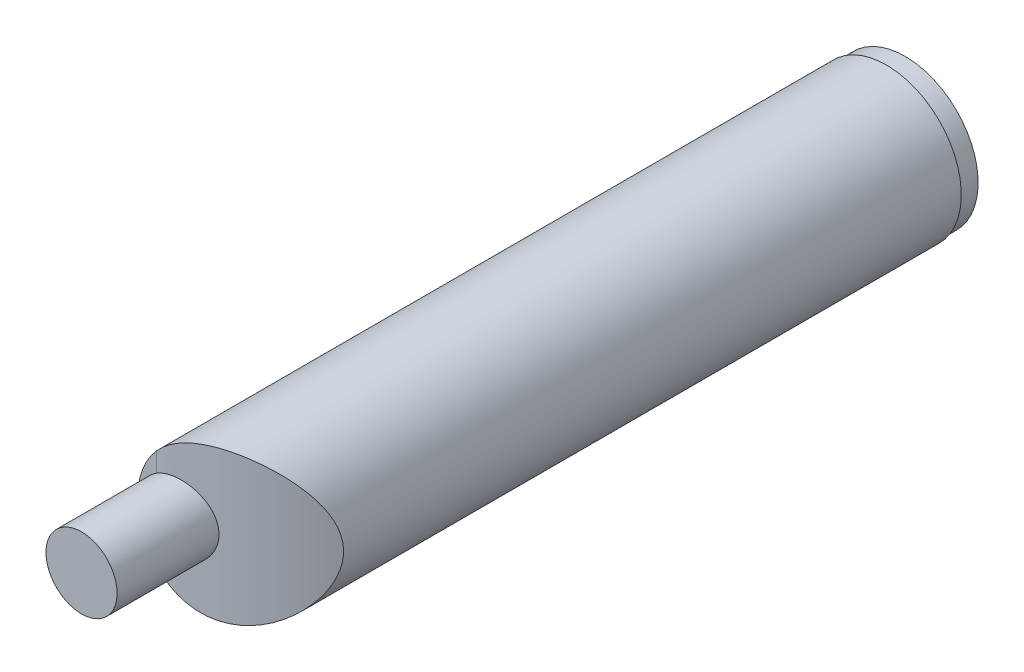
SolidWorks part; units mm, degrees
ref_plane "前视基准面" through (0, 0, 0) normal (0, 0, 1) x (1, 0, 0)
ref_plane "上视基准面" through (0, 0, 0) normal (0, 1, 0) x (1, 0, 0)
ref_plane "右视基准面" through (0, 0, 0) normal (1, 0, 0) x (0, 0, -1)
sketch "草图1" plane through (0, 0, 0) normal (0, 0, 1) x (1, 0, 0)
  circle A0 centre (0, 0) radius 4
  dimension "D1" = 8
extrude "凸台-拉伸1" add sketch "草图1" along normal blind 37
sketch "草图2" plane through (0, 0, 0) normal (0, 0, -1) x (-1, 0, 0)
  circle A1 centre (0, 0) radius 3.9
  circle A2 centre (0, 0) radius 4
  circle A3 centre (0, 0) radius 4 construction
  circle M1 centre (0, 0) radius 4
  dimension "D1" = 7.8
extrude "切除-拉伸1" cut sketch "草图2" against normal blind 1 contours A1 M1 region at (3.9887, 0, 0)
sketch "草图3" plane through (0, 0, 0) normal (0, 1, 0) x (1, 0, 0)
  line L0 (-3, -37) -> (4, -37)
  line L1 (4, -37) -> (4, -34)
  line L2 (4, -37) -> (4, -1) construction
  line L3 (-4, -37) -> (4, -37) construction
  line L4 (-4, -1) -> (-4, -37) construction
  arc A0 (-3, -37) -> (4, -34) centre (-3, -27.3333) ccw
  dimension "D1" = 3
  dimension "D2" = 1
extrude "切除-拉伸2" cut sketch "草图3" against normal through all both and the other way through all
sketch "草图4" plane through (0, 0, 37) normal (0, 0, 1) x (1, 0, 0)
  circle A0 centre (-2, 0) radius 1.9
  dimension "D1" = 3.8
  dimension "D2" = 2
extrude "凸台-拉伸2" add sketch "草图4" against normal up to next and the other way blind 5
sketch "草图5" plane through (0, 0, 0) normal (1, 0, 0) x (0, 0, -1)
  line L0 (0, -3.9) -> (0, 3.9) construction
  line L1 (-10, 0) -> (0, 0) construction
  line L2 (0, 3.5) -> (0.5, 3.5)
  line L3 (0.5, 3.5) -> (0.5, 0)
  line L4 (0.5, 0) -> (0, 0)
  arc A0 (-0.3158, 2.4931) -> (0, 0) centre (-10, 0) cw
  arc A1 (-0.3158, 2.4931) -> (0, 3.5) centre (0.6527, 2.7424) cw
  dimension "D1" = 10
  dimension "D2" = 1
  dimension "D3" = 3.5
  dimension "D4" = 0.5
revolve "切除-旋转3" cut sketch "草图5" angle 360 about L1
